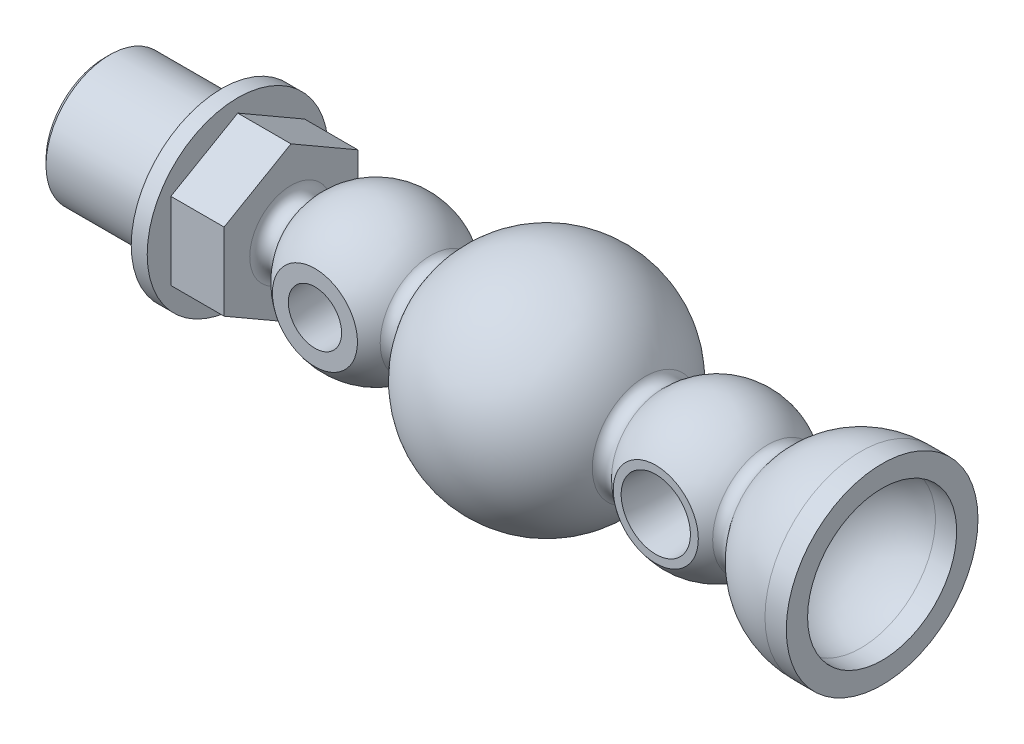
SolidWorks part; units mm, degrees
note: The reader was unsure of these and kept them because the rebuilt part matched: shared geometry of "Sketch2<3>", "Sketch2<4>".
ref_plane "Front Plane" through (0, 0, 0) normal (0, 0, 1) x (1, 0, 0)
ref_plane "Top Plane" through (0, 0, 0) normal (0, 1, 0) x (1, 0, 0)
ref_plane "Right Plane" through (0, 0, 0) normal (1, 0, 0) x (0, 0, -1)
sketch "Sketch2" plane through (0, 0, 0) normal (0, 1, 0) x (1, 0, 0)
  line L0 (-126, 0) -> (126, 0) construction
  line L1 (-166, 12) -> (-98, 12)
  line L2 (-96, 10) -> (-96, 5)
  line L3 (-96, 5) -> (-36.3318, 5)
  line L4 (36.3318, 5) -> (88.8281, 5)
  line L5 (118, 28) -> (126, 28)
  line L6 (126, 28) -> (126, 36)
  line L7 (126, 36) -> (118, 36)
  line L8 (-166, 12) -> (-166, 22)
  line L9 (-164, 24) -> (-124, 24)
  line L10 (-124, 24) -> (-124, 22)
  line L11 (-124, 22) -> (-122, 22)
  line L12 (-122, 22) -> (-122, 34)
  line L13 (-122, 34) -> (-116, 34)
  line L14 (-116, 34) -> (-116, 29)
  line L15 (-116, 29) -> (-96, 29)
  line L16 (-96, 29) -> (-96, 15.4919)
  line L17 (-79.9687, 23) -> (-48.0313, 23)
  line L19 (48.0313, 23) -> (79.9687, 23)
  line L20 (-166, 22) -> (-164, 24)
  arc A0 (-34.3679, 6.6216) -> (34.3679, 6.6216) centre (0, 0) cw
  arc A1 (90.7729, 6.5333) -> (118, 28) centre (118, 0) cw
  arc A2 (-37.0068, 19.862) -> (37.0068, 19.862) centre (0, 0) cw
  arc A3 (43.4648, 19.0344) -> (82.9583, 20.6054) centre (64, 0) cw
  arc A4 (88.9, 21.1941) -> (118, 36) centre (118, 0) cw
  arc A5 (-88.5, 13.5554) -> (-43.4648, 19.0344) centre (-64, 0) cw
  arc A6 (82.9583, 20.6054) -> (88.9, 21.1941) centre (85.6667, 23.549) ccw
  arc A7 (-43.4648, 19.0344) -> (-37.0068, 19.862) centre (-40.5312, 21.7536) ccw
  arc A8 (-96, 15.4919) -> (-88.5, 13.5554) centre (-92, 15.4919) ccw
  arc A9 (37.0068, 19.862) -> (43.4648, 19.0344) centre (40.5312, 21.7536) ccw
  arc A10 (-98, 12) -> (-96, 10) centre (-98, 10) cw
  arc A11 (88.8281, 5) -> (90.7729, 6.5333) centre (88.8281, 7) ccw
  arc A12 (34.3679, 6.6216) -> (36.3318, 5) centre (36.3318, 7) ccw
  arc A13 (-36.3318, 5) -> (-34.3679, 6.6216) centre (-36.3318, 7) ccw
  point P16 (-166, 24)
  point P36 (0, 0)
  dimension "D5" = 35
  dimension "D6" = 72
  dimension "D7" = 56
  dimension "D10" = 42
  dimension "D13" = 28
  dimension "D18" = 28
  dimension "D24" = 4
  dimension "D25" = 2
  dimension "D26" = 44
  dimension "D31" = 2
  dimension "D3" = 10
  dimension "D4" = 24
  dimension "D8" = 292
  dimension "D9" = 8
  dimension "D11" = 44
  dimension "D12" = 2
  dimension "D14" = 6
  dimension "D15" = 20
  dimension "D16" = 64
  dimension "D17" = 64
  dimension "D19" = 48
  dimension "D20" = 68
  dimension "D21" = 58
  dimension "D22" = 10
  dimension "D23" = 118
  dimension "D27" = 46
  dimension "D28" = 46
  dimension "D29" = 2
  dimension "D30" = 45
  dimension "D32" = 70
revolve "Revolve1" add sketch "Sketch2" angle 360 about L0
extrude "Cut-Extrude3" cut sketch "Sketch2<3>" against normal through all both and the other way through all contours L17
sketch "Sketch2<3>" plane through (0, 0, 0) normal (0, 1, 0) x (1, 0, 0) same geometry as "Sketch2"
extrude "Cut-Extrude4" cut sketch "Sketch2<4>" against normal through all both and the other way through all contours L19
sketch "Sketch2<4>" plane through (0, 0, 0) normal (0, 1, 0) x (1, 0, 0) same geometry as "Sketch2"
mirror "Mirror1" about plane through (0, 0, 0) normal (0, 0, 1) of "Cut-Extrude4", "Cut-Extrude3"
sketch "Sketch3" plane through (0, 0, 0) normal (0, 1, 0) x (1, 0, 0)
  line L0 (-48.0313, 23) -> (-79.9687, 23) construction
  line L1 (-48.0313, 23) -> (-79.9687, 23) construction
  line L2 (-79.9687, -23) -> (-48.0313, -23) construction
  line L3 (-79.9687, -23) -> (-48.0313, -23) construction
  line L5 (-74, -23) -> (-64, -23)
  line L6 (-64, -23) -> (-64, 23)
  line L8 (-74, -23) -> (-77, 23)
  line L9 (-77, 23) -> (-64, 23)
  dimension "D1" = 13
  dimension "D2" = 10
revolve "Cut-Revolve1" cut sketch "Sketch3" angle 360 about L6
sketch "Sketch4" plane through (0, 0, 0) normal (0, 1, 0) x (1, 0, 0)
  line L0 (48.0313, -23) -> (79.9687, -23) construction
  line L1 (79.9687, 23) -> (48.0313, 23) construction
  line L2 (48.0313, -23) -> (79.9687, -23) construction
  line L3 (79.9687, 23) -> (48.0313, 23) construction
  line L4 (54, 23) -> (51, -23)
  line L5 (51, -23) -> (64, -23)
  line L6 (64, -23) -> (64, 23)
  line L7 (64, 23) -> (54, 23)
  dimension "D1" = 10
  dimension "D2" = 13
revolve "Cut-Revolve2" cut sketch "Sketch4" angle 360 about L6
sketch "Sketch5" plane through (-96, 0, 0) normal (1, 0, 0) x (0, 0, -1)
  line L0 (23, -15.9687) -> (23, 15.9687) construction
  line L1 (25.1147, 14.5) -> (0, 29)
  line L2 (0, 29) -> (-25.1147, 14.5)
  line L3 (-25.1147, 14.5) -> (-25.1147, -14.5)
  line L4 (-25.1147, -14.5) -> (0, -29)
  line L5 (0, -29) -> (25.1147, -14.5)
  line L6 (25.1147, -14.5) -> (25.1147, 14.5)
  line L7 (23, -15.9687) -> (23, 15.9687) construction
  circle A0 centre (0, 0) radius 25.1147 construction
  circle A1 centre (0, 0) radius 29
  circle A2 centre (0, 0) radius 29 construction
  point P2 (0, 0)
  dimension "D1" = 0
extrude "Cut-Extrude5" cut sketch "Sketch5" against normal up to surface (20 mm away) flip side to cut up to face at (-116, 0, 29)
